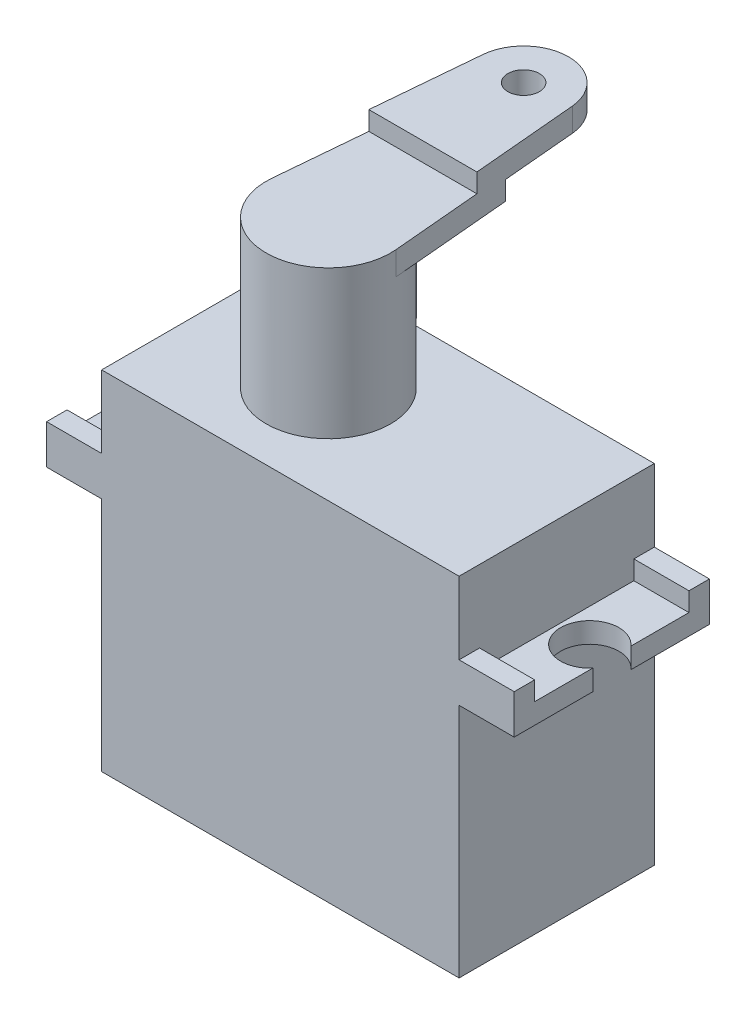
SolidWorks part; units mm, degrees
ref_plane "Front Plane" through (0, 0, 0) normal (0, 0, 1) x (1, 0, 0)
ref_plane "Top Plane" through (0, 0, 0) normal (0, 1, 0) x (1, 0, 0)
ref_plane "Right Plane" through (0, 0, 0) normal (1, 0, 0) x (0, 0, -1)
sketch "Sketch1" plane through (0, 0, 0) normal (0, 0, 1) x (1, 0, 0)
  line L0 (-11.35, -1.25) -> (-11.35, -16.25)
  line L1 (-11.35, 5.85) -> (11.35, 5.85)
  line L2 (-11.35, 5.85) -> (-11.35, 1.25)
  line L3 (-11.35, -16.25) -> (11.35, -16.25)
  line L4 (11.35, 5.85) -> (11.35, 1.25)
  line L5 (0, -16.25) -> (0, 5.85) construction
  line L6 (0, 0) -> (11.35, 0) construction
  line L7 (-14.85, 1.25) -> (-11.35, 1.25)
  line L8 (-14.85, 1.25) -> (-14.85, -1.25)
  line L9 (-14.85, -1.25) -> (-11.35, -1.25)
  line L10 (14.85, 1.25) -> (14.85, -1.25)
  line L11 (0, -1.25) -> (0, 1.25) construction
  line L12 (-14.85, 0) -> (-11.35, 0) construction
  line L13 (11.35, 1.25) -> (11.35, 0) construction
  line L14 (11.35, -1.25) -> (11.35, -16.25)
  line L15 (11.35, 0) -> (11.35, -1.25) construction
  line L16 (-11.35, 1.25) -> (0, 1.25) construction
  line L17 (11.35, 1.25) -> (14.85, 1.25)
  line L18 (-11.35, 0) -> (0, 0) construction
  line L19 (-11.35, 0) -> (0, 0) construction
  line L20 (11.35, 0) -> (14.85, 0) construction
  line L21 (-11.35, -1.25) -> (0, -1.25) construction
  line L22 (11.35, -1.25) -> (14.85, -1.25)
  line L23 (0, 1.25) -> (11.35, 1.25) construction
  line L24 (0, 0) -> (11.35, 0) construction
  line L25 (0, -1.25) -> (11.35, -1.25) construction
  line L26 (-11.35, -1.25) -> (-11.35, 1.25) construction
  point P13 (0, 0)
  point P14 (-11.35, 0)
  point P56 (0, 0)
  point P131 (0, 0)
  dimension "D1" = 22.7
  dimension "D2" = 22.1
  dimension "D3" = 2.5
  dimension "D4" = 3.5
  dimension "D5" = 15
extrude "Boss-Extrude1" add sketch "Sketch1" along normal blind 12.4
sketch "Sketch2" plane through (0, 1.25, 0) normal (0, 1, 0) x (1, 0, 0)
  line L0 (11.35, -12.4) -> (11.35, 0) construction
  line L1 (11.35, -1.3) -> (14.85, -1.3)
  line L2 (11.35, -1.3) -> (11.35, -11.1)
  line L3 (11.35, -11.1) -> (14.85, -11.1)
  line L4 (14.85, -1.3) -> (14.85, -11.1)
  line L5 (13.1, -11.1) -> (13.1, -1.3) construction
  line L6 (11.35, -6.2) -> (14.85, -6.2) construction
  line L7 (14.85, -12.4) -> (14.85, 0) construction
  line L8 (14.85, 0) -> (11.35, 0) construction
  line L9 (11.35, -6.2) -> (14.85, -6.2) construction
  line L10 (11.35, -6.2) -> (14.85, -6.2) construction
  line L11 (11.35, 0) -> (14.85, 0) construction
  line L12 (11.35, 0) -> (11.35, -12.4) construction
  line L13 (11.35, -12.4) -> (14.85, -12.4) construction
  line L14 (14.85, 0) -> (14.85, -12.4) construction
  arc A0 (14.85, -4.9907) -> (14.85, -7.4093) centre (13.45, -6.2) ccw
  arc A1 (14.85, -7.4093) -> (14.85, -4.9907) centre (13.45, -6.2) ccw construction
  point P16 (0, 0)
  point P19 (0, 0)
  point P20 (13.1, -6.2)
  point P21 (13.9075, -6.2)
  point P220 (13.1, -6.2)
  line M9 (11.35, 0) -> (11.35, -12.4)
  line M11 (14.85, -12.4) -> (14.85, 0)
  dimension "D2" = 3.7
  dimension "D3" = 2.1
  dimension "D1" = 1.3
extrude "Cut-Extrude1" cut sketch "Sketch2" against normal blind 1.2 contours A0 L1 L3 M11 M9 region at (13.1, 1.25, 1.4041)
extrude "Cut-Extrude2" cut sketch "Sketch2<3>" against normal blind 3 contours L4 A0 region at (13.3322, 1.25, 6.2)
sketch "Sketch2<3>" plane through (0, 1.25, 0) normal (0, 1, 0) x (1, 0, 0) same geometry as "Sketch2"
mirror "Mirror1" about plane through (0, 0, 0) normal (1, 0, 0) of "Cut-Extrude2", "Cut-Extrude1"
sketch "Sketch3" plane through (0, 5.85, 0) normal (0, 1, 0) x (1, 0, 0)
  line L0 (11.35, -6.2) -> (-11.35, -6.2) construction
  line L1 (11.35, -1.3) -> (11.35, -11.1) construction
  line L2 (-11.35, -1.3) -> (-11.35, -11.1) construction
  circle A0 centre (-3.15, -6.2) radius 3.95
  dimension "D2" = 7.9
  dimension "D1" = 14.5
extrude "TurnBase" add sketch "Sketch3" along normal blind 7.9
sketch "Sketch4" plane through (0, 13.75, 0) normal (0, 1, 0) x (1, 0, 0)
  line L0 (-3.15, -10.15) -> (-3.15, 9.05) construction
  line L1 (-5.9888, 6.4528) -> (-7.0844, -5.8496)
  line L3 (0.7844, -5.8496) -> (-0.3112, 6.4528)
  arc A0 (-7.0844, -5.8496) -> (0.7844, -5.8496) centre (-3.15, -6.2) ccw
  arc A1 (-0.3112, 6.4528) -> (-5.9888, 6.4528) centre (-3.15, 6.2) ccw
  circle A2 centre (-3.15, -6.2) radius 3.95 construction
  arc A3 (0.7844, -5.8496) -> (-3.15, -2.25) centre (-3.15, -6.2) ccw construction
  arc A4 (-3.15, -2.25) -> (-7.0844, -5.8496) centre (-3.15, -6.2) ccw construction
  arc A5 (-5.9888, 6.4528) -> (-3.15, 3.35) centre (-3.15, 6.2) ccw construction
  arc A6 (-3.15, 3.35) -> (-0.3112, 6.4528) centre (-3.15, 6.2) ccw construction
  dimension "D1" = 5.7
  dimension "D2" = 19.2
extrude "Boss-Extrude3" add sketch "Sketch4" along normal blind 2.7
sketch "Sketch6" plane through (0, 0, 0) normal (1, 0, 0) x (0, 0, -1)
  line L0 (6.4528, 13.75) -> (9.05, 13.75) construction
  line L1 (9.05, 13.75) -> (1.8, 13.75)
  line L2 (9.05, 13.75) -> (9.05, 14.95)
  line L3 (9.05, 14.95) -> (1.8, 14.95)
  line L4 (1.8, 13.75) -> (1.8, 14.95)
  line L5 (-2.25, 12.0614) -> (-10.15, 12.0614) construction
  line L6 (-2.25, 5.85) -> (-2.25, 13.75) construction
  line L7 (-10.15, 16.45) -> (-10.15, 5.85) construction
  line L8 (-6.2, 12.0614) -> (-6.2, 16.45) construction
  line L9 (-5.8496, 16.45) -> (-10.15, 16.45) construction
  line L11 (-10.15, 16.45) -> (-0.2, 16.45)
  line L12 (-10.15, 16.45) -> (-10.15, 15.25)
  line L13 (-10.15, 15.25) -> (-0.2, 15.25)
  line L14 (-0.2, 16.45) -> (-0.2, 15.25)
  point P21 (1.8, 14.35)
  dimension "D1" = 8
  dimension "D2" = 1.2
  dimension "D3" = 1.2
  dimension "D4" = 2
extrude "Cut-Extrude3" cut sketch "Sketch6" against normal through all and the other way through all
sketch "Sketch7" plane through (0, 16.45, 0) normal (0, 1, 0) x (1, 0, 0)
  circle A0 centre (-3.15, 6.2) radius 1
  circle A1 centre (-3.15, 6.2) radius 2.85 construction
  arc A2 (-0.3112, 6.4528) -> (-5.9888, 6.4528) centre (-3.15, 6.2) ccw construction
  point P3 (-3.4982, 4.5818)
  point P7 (-3.15, 6.2)
  dimension "D1" = 2
extrude "Cut-Extrude4" cut sketch "Sketch7" against normal through all
